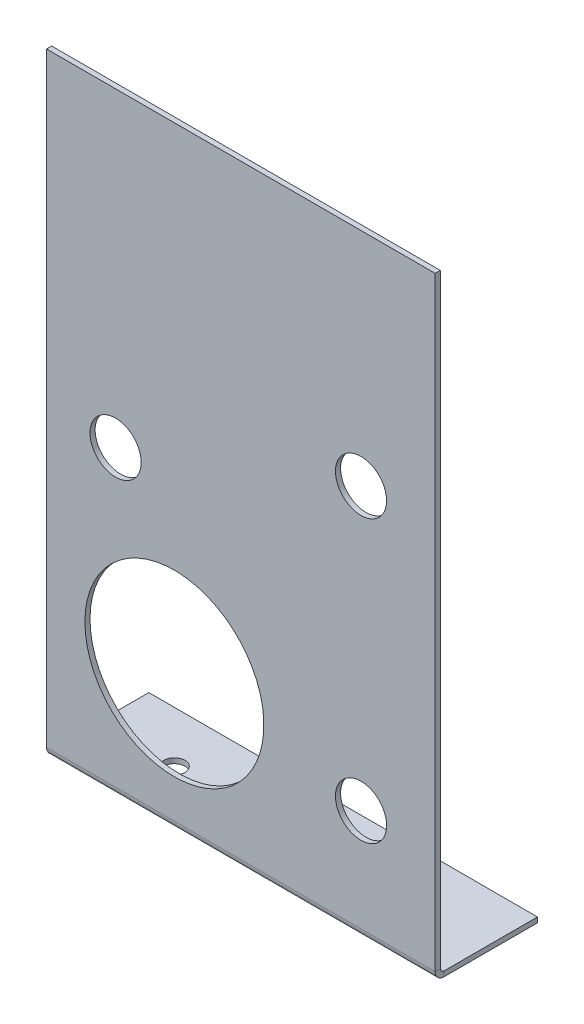
SolidWorks part; units mm, degrees
note: The reader was unsure of these and kept them because the rebuilt part matched: flange length of "Edge-Flange1".
material "AISI 1020 Steel, Cold Rolled"
ref_plane "Front Plane" through (0, 0, 0) normal (0, 0, 1) x (1, 0, 0)
ref_plane "Top Plane" through (0, 0, 0) normal (0, 1, 0) x (1, 0, 0)
ref_plane "Right Plane" through (0, 0, 0) normal (1, 0, 0) x (0, 0, -1)
sketch "Sketch2" plane through (0, 0, 0) normal (0, 0, 1) x (1, 0, 0)
  line L1 (-38, -60) -> (38, -60)
  line L2 (-38, -60) -> (-38, 60)
  line L3 (-38, 60) -> (38, 60)
  line L4 (38, -60) -> (38, 60)
  line L5 (-38, -60) -> (38, 60) construction
  line L6 (-38, 60) -> (38, -60) construction
  point P0 (0, 0)
  dimension "D1" = 76
  dimension "D2" = 120
base flange "Base-Flange1" sketch "Sketch2" thickness 1 reverse thickness direction no parameters "D1"=0.7366
edge flange "Edge-Flange1" sketch "Sketch9" flange angle 90 flange length 20 flange position material inside bend radius 0.7366 thickness 1 relief rectangular parameters "D6"=10
sketch "Sketch9" plane through (0, -60, -1) normal (0, -1, 0) x (-1, 0, 0)
  line L0 (38, 0) -> (-38, 0) construction
  line L1 (38, 0) -> (-38, 0)
  line L2 (-38, 0) -> (-38, 19)
  line L3 (-38, 19) -> (38, 19)
  line L4 (38, 19) -> (38, 0)
bend "EdgeBend1" bend radius 0.7366 bend angle 90 parameters "D5"=1
sketch "Sketch10" plane through (0, -59, 0) normal (0, 1, 0) x (1, 0, 0)
  line L0 (-38, 1.7366) -> (-38, 20) construction
  line L1 (38, 20) -> (38, 1.7366) construction
  line L2 (-38, 20) -> (38, 20) construction
  circle A0 centre (-23, 10) radius 2.064
  circle A1 centre (23, 10) radius 2.064
  dimension "D1" = 15
  dimension "D2" = 15
  dimension "D3" = 46
  dimension "D4" = 10
extrude "Cut-Extrude1" cut sketch "Sketch10" against normal blind 1 normal cut yes
sketch "Sketch11" plane through (0, 0, -1) normal (0, 0, -1) x (-1, 0, 0)
  line L1 (38, -58.2634) -> (-38, -58.2634) construction
  line L3 (38, 60) -> (38, -58.2634) construction
  line L4 (-38, -58.2634) -> (-38, 60) construction
  circle A0 centre (-23.5, -38.2634) radius 5
  circle A1 centre (13, -33.2634) radius 17.5
  circle A2 centre (24.5, -0.7634) radius 5
  circle A3 centre (-23.5, 16.7366) radius 5
  point P8 (0, 0)
  dimension "D1" = 10
  dimension "D2" = 35
  dimension "D3" = 10
  dimension "D4" = 10
  dimension "D5" = 20
  dimension "D6" = 13.5
  dimension "D7" = 57.5
  dimension "D8" = 25
  dimension "D9" = 14.5
  dimension "D10" = 14.5
  dimension "D11" = 75
  dimension "D12" = 25
extrude "Cut-Extrude2" cut sketch "Sketch11" against normal blind 1 normal cut yes
sketch "Bend-Lines1" [suppressed] plane through (0, 0, 0) normal (0, 1, 0) x (1, 0, 0)
sketch "Bounding-Box1" [suppressed] plane through (0, 0, 0) normal (0, 1, 0) x (1, 0, 0)
sheet metal parameters "Sheet-Metal1" thickness 1 parameters "D1"=0.7366
flat pattern "Flat-Pattern1" [suppressed]
sketch "Bend-Lines2" plane through (0, 0, 0) normal (0, 1, 0) x (1, 0, 0)
sketch3d "Bounding-Box2" [suppressed]
  line L0 (-38, 50, 0) -> (-38, -50, 0) construction
  line L1 (38, 50, 0) -> (38, -50, 0) construction
  line L2 (-38, 50, 0) -> (38, 50, 0) construction
  line L3 (-38, -50, 0) -> (38, -50, 0) construction
sheet metal parameters "Sheet-Metal2" thickness 1 parameters "D1"=0.7366
flat pattern "Flat-Pattern1"
sketch "Bend-Lines2" plane through (0, 0, 0) normal (0, 0, 1) x (1, 0, 0)
  line L0 (-38, -49.2346) -> (38, -49.2346) construction
  line L1 (-38, -49.2346) -> (38, -49.2346) construction
sketch3d "Bounding-Box2" [suppressed]
  line L0 (38, 50, 0) -> (38, -68.4692, 0) construction
  line L1 (-38, 50, 0) -> (-38, -68.4692, 0) construction
  line L2 (38, 50, 0) -> (-38, 50, 0) construction
  line L3 (38, -68.4692, 0) -> (-38, -68.4692, 0) construction
bend of the flat pattern "Flatten-<EdgeBend1>1"
sheet metal parameters "Sheet-Metal3" thickness 1 parameters "D1"=0.7366
flat pattern "Flat-Pattern1"
sketch "Bend-Lines2" plane through (0, 0, 0) normal (0, 0, 1) x (1, 0, 0)
  line L0 (-38, -49.2346) -> (38, -49.2346) construction
  line L1 (-38, -49.2346) -> (38, -49.2346) construction
sketch3d "Bounding-Box2" [suppressed]
  line L0 (38, 50, 0) -> (38, -68.4692, 0) construction
  line L1 (-38, 50, 0) -> (-38, -68.4692, 0) construction
  line L2 (38, 50, 0) -> (-38, 50, 0) construction
  line L3 (38, -68.4692, 0) -> (-38, -68.4692, 0) construction
bend of the flat pattern "Flatten-<EdgeBend1>1"
sheet metal parameters "Sheet-Metal4" thickness 1 parameters "D1"=0.7366
flat pattern "Flat-Pattern1"
sketch "Bend-Lines2" plane through (0, 0, 0) normal (0, 0, 1) x (1, 0, 0)
  line L0 (-38, -59.2346) -> (38, -59.2346) construction
  line L1 (-38, -59.2346) -> (38, -59.2346) construction
sketch3d "Bounding-Box2" [suppressed]
  line L0 (38, 60, 0) -> (38, -78.4692, 0) construction
  line L1 (-38, 60, 0) -> (-38, -78.4692, 0) construction
  line L2 (38, 60, 0) -> (-38, 60, 0) construction
  line L3 (38, -78.4692, 0) -> (-38, -78.4692, 0) construction
bend of the flat pattern "Flatten-<EdgeBend1>1"
